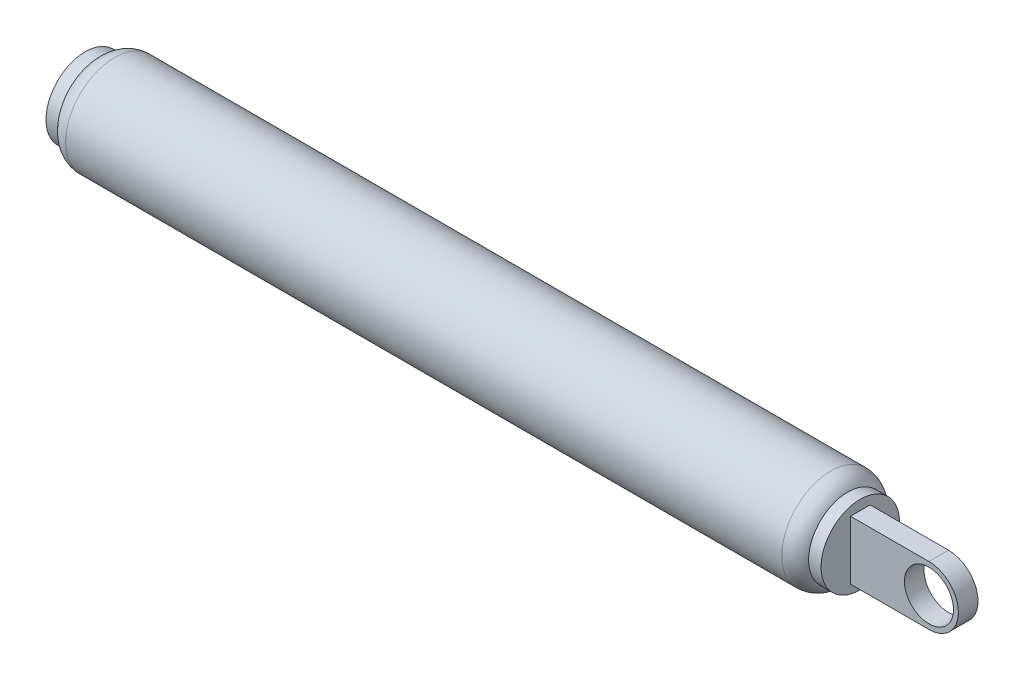
SolidWorks part; units mm, degrees
ref_plane "Front Plane" through (0, 0, 0) normal (0, 0, 1) x (1, 0, 0)
ref_plane "Top Plane" through (0, 0, 0) normal (0, 1, 0) x (1, 0, 0)
ref_plane "Right Plane" through (0, 0, 0) normal (1, 0, 0) x (0, 0, -1)
ref_plane "Plane1" through (0, 0, 0) normal (0, 0, -1) x (-1, 0, 0)
sketch "Sketch1" plane through (0, 0, 0) normal (0, 0, -1) x (-1, 0, 0)
  line L0 (-39.5, 4) -> (-39.5, 0)
  line L1 (-39.5, 0) -> (39.5, 0)
  line L2 (39.5, 0) -> (39.5, 4)
  line L3 (39.5, 4) -> (38.2321, 4)
  line L4 (36.5, 5) -> (-36.5, 5)
  line L5 (-38.2321, 4) -> (-39.5, 4)
  line L6 (-39.5, 0) -> (39.5, 0) construction
  arc A0 (38.2321, 4) -> (36.5, 5) centre (36.5, 3) ccw
  arc A1 (-36.5, 5) -> (-38.2321, 4) centre (-36.5, 3) ccw
revolve "Revolve1" add sketch "Sketch1" angle 360 about L6 reverse direction yes
ref_plane "Plane2" through (0, 0, 1) normal (0, 0, 1) x (1, 0, 0)
sketch "Sketch2" plane through (0, 0, 1) normal (0, 0, 1) x (1, 0, 0)
  line L0 (47.5, 3) -> (39.5, 3)
  line L1 (39.5, 3) -> (39.5, -3)
  line L2 (39.5, -3) -> (47.5, -3)
  arc A0 (47.5, -3) -> (47.5, 3) centre (47.5, 0) ccw
extrude "Boss-Extrude1" add sketch "Sketch2" against normal blind 2
hole_wizard "Ø6.0 (6) Diameter Hole1" positions "Sketch4" profile "Sketch3" hole size "Ø6.0" standard "ANSI Metric"
sketch "Sketch4" plane through (-39.5, 0, 0) normal (-1, 0, 0) x (0, 0, 1)
  point P0 (0, 0)
sketch "Sketch3" plane through (-39.5, 0, 0) normal (0, 1, 0) x (0, 0, 1)
  line L0 (0, 0) -> (0, 25)
  line L1 (0, 25) -> (3, 25)
  line L2 (3, 25) -> (3, 0)
  line L5 (3, 0) -> (0, 0)
  line L10 (0, 25) -> (-3, 25) construction
  line L11 (0, -6.35) -> (0, 107.95) construction
  dimension "Hole Dia." = 6
  dimension "Hole Depth" = 25
  dimension "Drill Angle" = 180
hole_wizard "Ø5.0 (5) Diameter Hole1" positions "Sketch6" profile "Sketch5" hole size "Ø5.0" standard "ANSI Metric"
sketch "Sketch6" plane through (0, 0, -1) normal (0, 0, -1) x (-1, 0, 0)
  point P0 (-47.5, 0)
sketch "Sketch5" plane through (47.5, 0, -1) normal (1, 0, 0) x (0, 1, 0)
  line L0 (0, 0) -> (0, 6)
  line L1 (0, 6) -> (2.5, 6)
  line L2 (2.5, 6) -> (2.5, 0)
  line L5 (2.5, 0) -> (0, 0)
  line L11 (0, -6.35) -> (0, 107.95) construction
  dimension "Thru Hole Dia." = 5
  dimension "Thru Hole Depth" = 6
